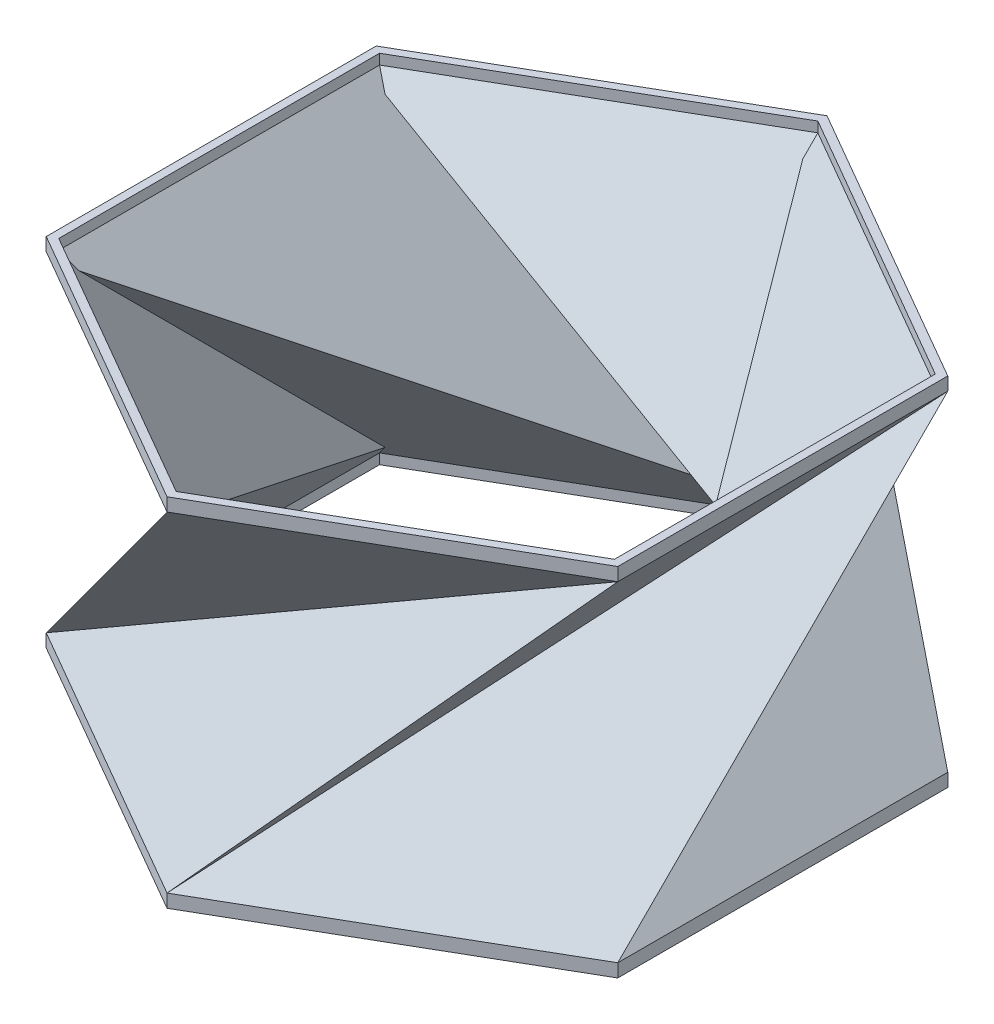
SolidWorks part; units mm, degrees
ref_plane "정면" through (0, 0, 0) normal (0, 0, 1) x (1, 0, 0)
ref_plane "윗면" through (0, 0, 0) normal (0, 1, 0) x (1, 0, 0)
ref_plane "우측면" through (0, 0, 0) normal (1, 0, 0) x (0, 0, -1)
sketch "스케치1" plane through (0, 0, 0) normal (0, 1, 0) x (1, 0, 0)
  line L0 (-55, 0) -> (55, 0) construction
  line L1 (21.6506, -12.5) -> (21.6506, 12.5)
  line L2 (21.6506, 12.5) -> (0, 25)
  line L3 (0, 25) -> (-21.6506, 12.5)
  line L4 (-21.6506, 12.5) -> (-21.6506, -12.5)
  line L5 (-21.6506, -12.5) -> (0, -25)
  line L6 (0, -25) -> (21.6506, -12.5)
  circle A0 centre (0, 0) radius 21.6506 construction
  point P11 (0, 0)
  point P12 (0, 0)
  dimension "D1" = 50
extrude "보스-돌출1" add sketch "스케치1" along normal blind 25
ref_plane "평면1" through (-6.1859, 10.7143, 10.7143) normal (-0.378, 0.6547, 0.6547) x (0.9258, 0.2673, 0.2673)
sketch "스케치2" plane through (-6.1859, 10.7143, 10.7143) normal (-0.378, 0.6547, 0.6547) x (0.9258, 0.2673, 0.2673)
  line L0 (-16.7038, -8.8388) -> (30.0669, 8.8388)
  line L1 (30.0669, 8.8388) -> (6.6815, -17.6777)
sketch "스케치3" plane through (-10.8253, 0, 18.75) normal (-0.5, 0, 0.866) x (0.866, 0, 0.5)
  line L0 (-12.5, 0) -> (12.5, 25)
ref_plane "평면2" through (-21.6506, 0, 12.5) normal (0.866, 0.5, 0) x (0, 0, -1)
sketch "스케치4" plane through (-21.6506, 0, 12.5) normal (0.866, 0.5, 0) x (0, 0, -1)
  line L0 (0, 0) -> (-12.5, -10.8253) construction
  line L1 (0, 0) -> (-12.5, 10.8253) construction
  line L2 (0, 0) -> (-12.5, -10.8253)
  line L3 (0, 0) -> (-12.5, 10.8253)
  line L4 (-12.5, 10.8253) -> (-12.5, -10.8253)
  point P2 (-11.6474, -10.8253)
  point P4 (0, 0)
extrude "컷-돌출1" cut sketch "스케치4" along normal up to vertex (50 mm away) up to point (21.6506, 25, 12.5)
pattern_circular "원형 패턴1" count 6 over 360 about axis through (0, 25, 0) along (0, 1, 0) of "컷-돌출1"
sketch "스케치5" plane through (0, 25, 0) normal (0, 1, 0) x (1, 0, 0)
  line L6 (0, -25) -> (21.6506, -12.5)
  line L7 (21.6506, -12.5) -> (21.6506, 12.5)
  line L8 (21.6506, 12.5) -> (0, 25)
  line L9 (0, 25) -> (-21.6506, 12.5)
  line L10 (-21.6506, 12.5) -> (-21.6506, -12.5)
  line L11 (-21.6506, -12.5) -> (0, -25)
  line L12 (0, -25) -> (21.6506, -12.5)
  line L13 (21.6506, -12.5) -> (21.6506, 12.5)
  line L14 (21.6506, 12.5) -> (0, 25)
  line L15 (0, 25) -> (-21.6506, 12.5)
  line L16 (-21.6506, 12.5) -> (-21.6506, -12.5)
  line L17 (-21.6506, -12.5) -> (0, -25)
  dimension "D1" = 0
extrude "보스-돌출2" add sketch "스케치5" along normal blind 1
sketch "스케치6" plane through (0, 0, 0) normal (0, -1, 0) x (1, 0, 0)
  line L6 (21.6506, 12.5) -> (0, 25)
  line L7 (0, 25) -> (-21.6506, 12.5)
  line L8 (-21.6506, 12.5) -> (-21.6506, -12.5)
  line L9 (-21.6506, -12.5) -> (0, -25)
  line L10 (0, -25) -> (21.6506, -12.5)
  line L11 (21.6506, -12.5) -> (21.6506, 12.5)
  line L12 (21.6506, 12.5) -> (0, 25)
  line L13 (0, 25) -> (-21.6506, 12.5)
  line L14 (-21.6506, 12.5) -> (-21.6506, -12.5)
  line L15 (-21.6506, -12.5) -> (0, -25)
  line L16 (0, -25) -> (21.6506, -12.5)
  line L17 (21.6506, -12.5) -> (21.6506, 12.5)
  dimension "D1" = 0
extrude "보스-돌출3" add sketch "스케치6" along normal blind 1
shell "쉘1" thickness 0.6 removed face at (0, 26, 0) removed face at (0, -1, 0)
